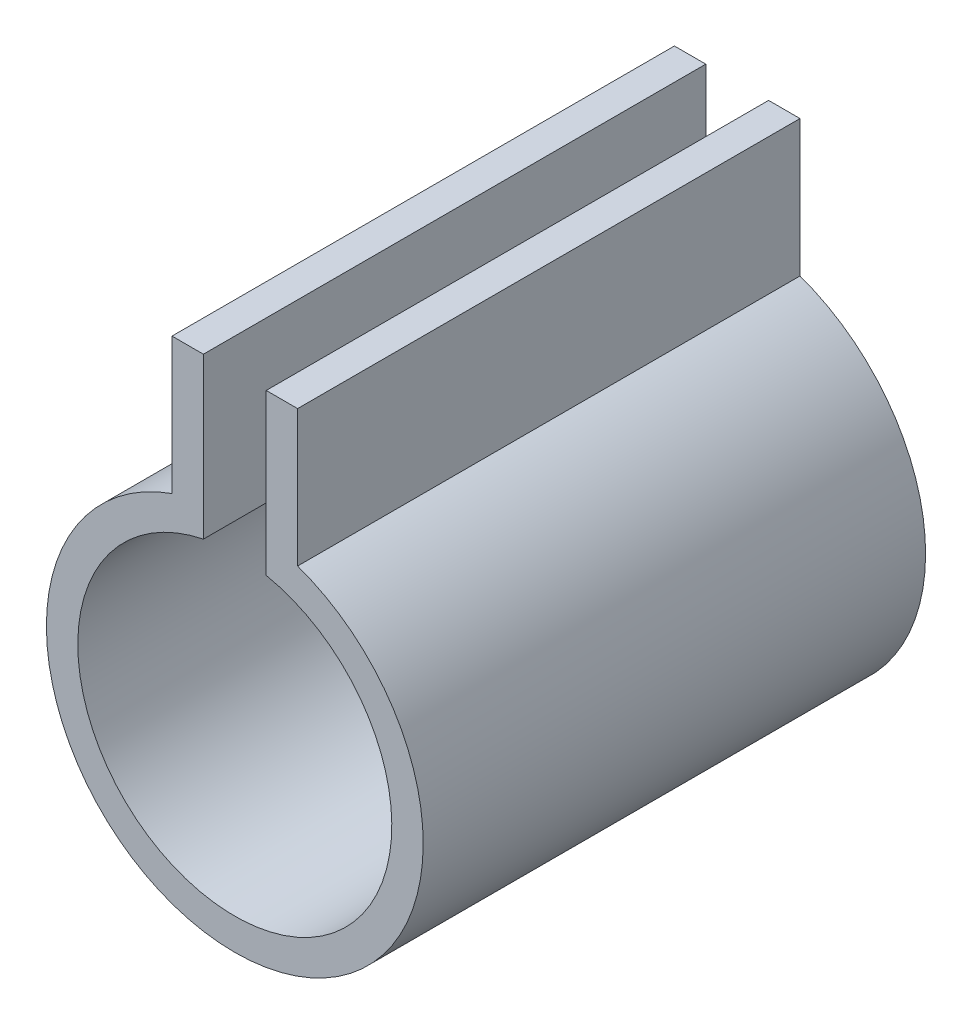
SolidWorks part; units mm, degrees
ref_plane "Front" through (0, 0, 0) normal (0, 0, 1) x (1, 0, 0)
ref_plane "Top" through (0, 0, 0) normal (0, 1, 0) x (1, 0, 0)
ref_plane "Right" through (0, 0, 0) normal (1, 0, 0) x (0, 0, -1)
sketch "Sketch2" plane through (0, 0, 0) normal (0, 0, 1) x (1, 0, 0)
  line L0 (0, 0) -> (0, 31.75) construction
  line L1 (3.175, 22.86) -> (3.175, 31.75)
  line L2 (3.175, 31.75) -> (6.35, 31.75)
  line L3 (6.35, 31.75) -> (6.35, 17.9605)
  line L4 (3.175, 31.75) -> (0, 31.75) construction
  line L5 (3.175, 22.86) -> (3.175, 15.5543)
  line L6 (-6.35, 31.75) -> (-6.35, 17.9605)
  line L7 (-3.175, 31.75) -> (-6.35, 31.75)
  line L8 (-3.175, 22.86) -> (-3.175, 15.5543)
  line L9 (-3.175, 22.86) -> (-3.175, 31.75)
  arc A0 (-3.175, 15.5543) -> (3.175, 15.5543) centre (0, 0) ccw
  arc A1 (-6.35, 17.9605) -> (6.35, 17.9605) centre (0, 0) ccw
  dimension "D1" = 31.75
  dimension "D2" = 38.1
  dimension "D3" = 3.175
  dimension "D4" = 3.175
  dimension "D5" = 8.89
  dimension "D6" = 31.75
extrude "Boss-Extrude1" add sketch "Sketch2" along normal blind 50.8
